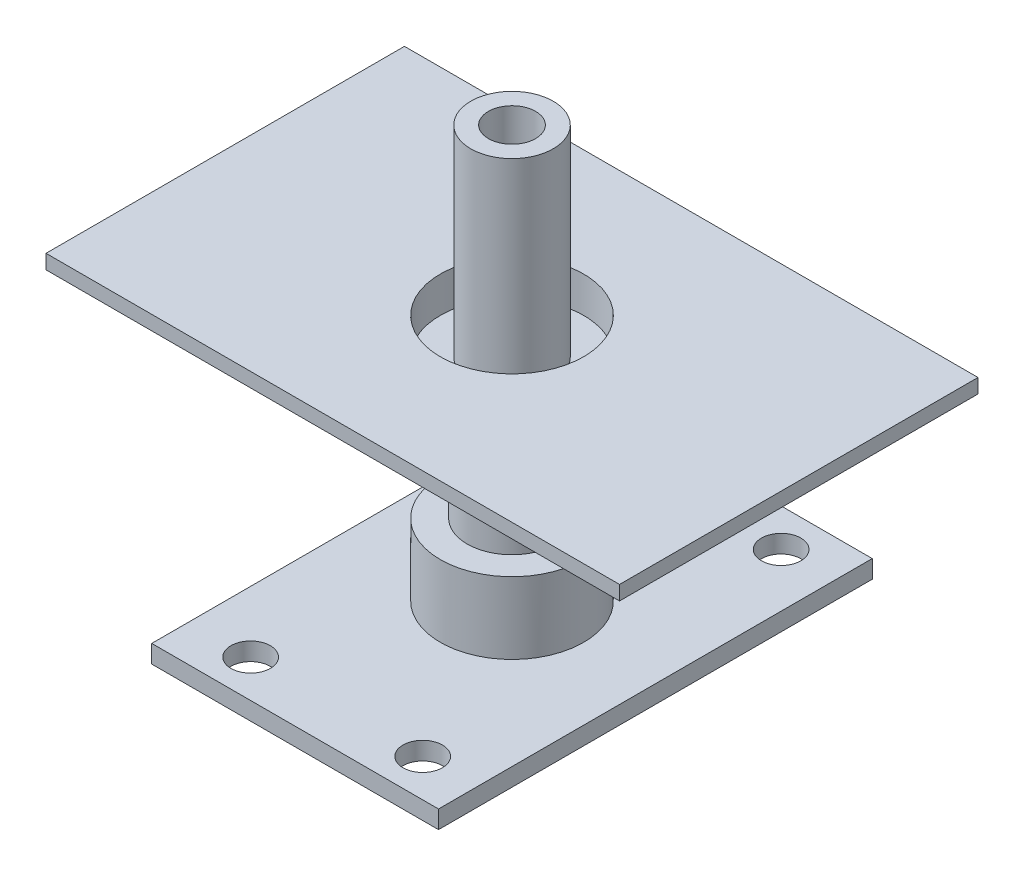
SolidWorks part; units mm, degrees
ref_plane "Front Plane" through (0, 0, 0) normal (0, 0, 1) x (1, 0, 0)
ref_plane "Top Plane" through (0, 0, 0) normal (0, 1, 0) x (1, 0, 0)
ref_plane "Right Plane" through (0, 0, 0) normal (1, 0, 0) x (0, 0, -1)
sketch "Sketch1" plane through (0, 0, 0) normal (0, 1, 0) x (1, 0, 0)
  line L0 (0, 60.5) -> (0, -60.5) construction
  line L9 (40, 60.5) -> (-40, 60.5)
  line L10 (40, 60.5) -> (40, -60.5)
  line L11 (40, -60.5) -> (-40, -60.5)
  line L12 (-40, 60.5) -> (-40, -60.5)
  line L13 (-40, 0) -> (40, 0) construction
  circle A9 centre (-22.9125, 50) radius 5.5
  circle A10 centre (25.0875, 50) radius 5.5
  circle A11 centre (-22.9125, -50) radius 5.5
  circle A12 centre (25.0875, -50) radius 5.5
  point P0 (33.7453, 25.6619)
  point P25 (0, 0)
  dimension "D5" = 121
  dimension "D6" = 80
extrude "Boss-Extrude1" add sketch "Sketch1" along normal blind 5
sketch "Sketch2" plane through (0, 5, 0) normal (0, 1, 0) x (1, 0, 0)
  line L0 (0, 60.5) -> (0, -60.5) construction
  line L1 (40, 60.5) -> (-40, 60.5) construction
  line L2 (-40, -60.5) -> (40, -60.5) construction
  line L3 (-40, 0) -> (40, 0) construction
  line L4 (-40, 60.5) -> (-40, -60.5) construction
  line L5 (40, -60.5) -> (40, 60.5) construction
  circle A0 centre (0, 0) radius 20
  circle A1 centre (0, 0) radius 12.5
  dimension "D1" = 40
  dimension "D2" = 25
extrude "Boss-Extrude2" add sketch "Sketch2" along normal blind 20
sketch "Sketch4" plane through (0, 5, 0) normal (0, 1, 0) x (1, 0, 0)
  circle A0 centre (0, 0) radius 12.5
extrude "Boss-Extrude3" add sketch "Sketch4" along normal blind 55 separate body
sketch "Sketch5" plane through (0, 60, 0) normal (0, 1, 0) x (1, 0, 0)
  circle A0 centre (0, 0) radius 6.5869
extrude "Cut-Extrude1" cut sketch "Sketch5" against normal blind 30
sketch "Sketch9" plane through (0, 60, 0) normal (0, 1, 0) x (1, 0, 0)
  circle A0 centre (0, 0) radius 6.5869
  circle A1 centre (0, 0) radius 11.5
  dimension "D1" = 23
extrude "Boss-Extrude6" add sketch "Sketch9" along normal blind 60
sketch "Sketch6" plane through (0, 60, 0) normal (0, 1, 0) x (1, 0, 0)
  line L1 (-80, -50) -> (80, -50)
  line L2 (-80, -50) -> (-80, 50)
  line L3 (-80, 50) -> (80, 50)
  line L4 (80, -50) -> (80, 50)
  line L5 (-80, -50) -> (80, 50) construction
  line L6 (-80, 50) -> (80, -50) construction
  circle A0 centre (0, 0) radius 12.5
  point P0 (0, 0)
  dimension "D1" = 25
  dimension "D2" = 160
  dimension "D3" = 100
extrude "Boss-Extrude4" add sketch "Sketch6" along normal blind 4 from offset 10 separate body
sketch "Sketch7" plane through (0, 60, 0) normal (0, 1, 0) x (-1, 0, 0)
  circle A0 centre (0, 0) radius 25
  dimension "D2" = 50
sketch "Sketch10" plane through (0, 74, 0) normal (0, 1, 0) x (1, 0, 0)
  circle A0 centre (0, 0) radius 22.5
  circle A2 centre (0, 0) radius 11.5
extrude "Boss-Extrude7" add sketch "Sketch10" against normal up to surface (14 mm away) up to face at (0, 60, 11.5)
sketch "Sketch8" plane through (0, 74, 0) normal (0, 1, 0) x (1, 0, 0)
  circle A1 centre (0, 0) radius 20
  circle A2 centre (0, 0) radius 11.5
  dimension "D2" = 40
extrude "Cut-Extrude5" cut sketch "Sketch8" against normal blind 10
